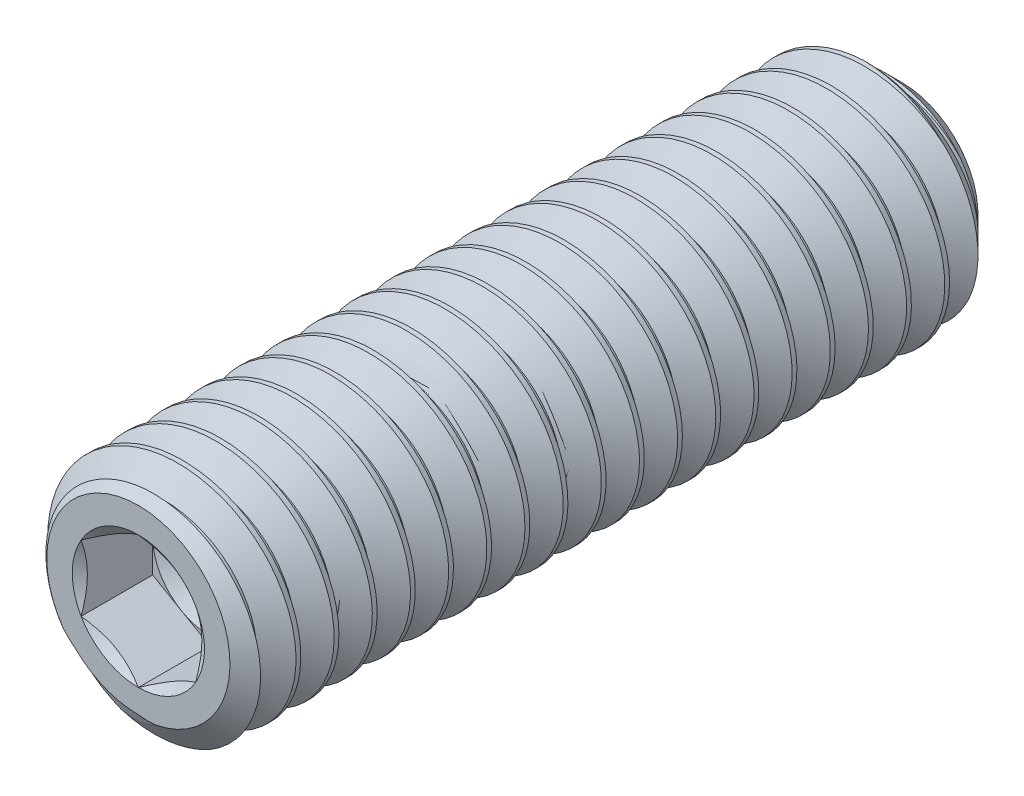
SolidWorks part; units mm, degrees
ref_plane "Front" through (0, 0, 0) normal (0, 0, 1) x (1, 0, 0)
ref_plane "Top" through (0, 0, 0) normal (0, 1, 0) x (1, 0, 0)
ref_plane "Right" through (0, 0, 0) normal (1, 0, 0) x (0, 0, -1)
sketch "Sketch22" plane through (0, 0, 0) normal (1, 0, 0) x (0, 0, -1)
  line L0 (-5, 0) -> (-5, 1.2)
  line L1 (-5, 1.2) -> (-4.7899, 1.5)
  line L2 (-4.7899, 1.5) -> (4.5, 1.5)
  line L3 (4.5, 1.5) -> (5, 1)
  line L4 (-0.145, 1.5) -> (-0.145, -1.5) construction
  line L5 (5, 0) -> (-5, 0)
  line L6 (-5, 1.2) -> (-5, -1.2) construction
  line L7 (5, 0) -> (5, 1)
  point P11 (-0.145, 0)
  dimension "D1" = 2.4
  dimension "Dia" = 3
  dimension "D2" = 0.5
  dimension "Length" = 10
  dimension "D3" = 35
  dimension "D6" = 45
revolve "Revolve1" add sketch "Sketch22" angle 360 about L5
ref_plane "Plane1" through (0, 0, -5) normal (0, 0, 1) x (1, 0, 0)
sketch "Sketch27" plane through (0, 0, -5) normal (0, 0, 1) x (1, 0, 0)
  circle A0 centre (0, 0) radius 1.5 construction
  circle A1 centre (0, 0) radius 1.5
curve "Helix/Spiral1" pitch 0.5 height 10.5 radius 1.5 centre (0, 0, -5) axis (0, 0, 1) start towards (0, 1, 0)
sketch "Sketch28" plane through (0, 0, 0) normal (1, 0, 0) x (0, 0, -1)
  line L0 (5, 1.5) -> (5.4375, 1.5)
  line L1 (5.4375, 1.5) -> (5.25, 1.1752)
  line L2 (5.25, 1.1752) -> (5.1875, 1.1752)
  line L3 (5.1875, 1.1752) -> (5, 1.5)
  line L4 (5.0937, 1.3376) -> (5.3437, 1.3376) construction
  line L6 (-4.7899, 1.5) -> (4.5, 1.5) construction
  dimension "D1" = 0.0625
  dimension "D2" = 0.25
  dimension "D3" = 60
sweep "Cut-Sweep2" cut profiles "Sketch28" path "Helix/Spiral1"
sketch "Sketch23" plane through (0, 0, 5) normal (0, 0, 1) x (1, 0, 0)
  line L1 (0, 0.866) -> (-0.75, 0.433)
  line L2 (-0.75, 0.433) -> (-0.75, -0.433)
  line L3 (-0.75, -0.433) -> (0, -0.866)
  line L4 (0, -0.866) -> (0.75, -0.433)
  line L5 (0.75, -0.433) -> (0.75, 0.433)
  line L6 (0.75, 0.433) -> (0, 0.866)
  circle A0 centre (0, 0) radius 0.75 construction
  dimension "Hex" = 1.5
extrude "Cut-Extrude10" cut sketch "Sketch23" against normal blind 0.9375
sketch "Sketch24" plane through (0, 0, 5) normal (0, 0, 1) x (1, 0, 0)
  circle A0 centre (0, 0) radius 0.866
extrude "Cut-Extrude11" cut sketch "Sketch24" against normal through all draft 55
sketch "Sketch26" plane through (0, 0, 4.0625) normal (0, 0, 1) x (1, 0, 0)
  circle A0 centre (0, 0) radius 0.75 construction
  circle A1 centre (0, 0) radius 0.75
extrude "Cut-Extrude12" cut sketch "Sketch26" against normal through all draft 60
sketch "Sketch30" plane through (0, 0, 0) normal (1, 0, 0) x (0, 0, -1)
  line L0 (-4.7899, 1.5) -> (4.5, 1.5) construction
  line L1 (-5, 0) -> (-5, 1.2) construction
  line L2 (5, 0) -> (5, 1) construction
  point P0 (-5, 1.5)
  point P1 (5, 1.5)
  point P2 (5, -1.5)
  point P11 (3.75, -1.5)
  dimension "D1" = 1.25
equation "\"D1@Sketch28\" = \"D4@Helix/Spiral1\" * .125"
equation "\"D2@Sketch28\" = \"D4@Helix/Spiral1\" * .5"
equation "\"D3@Helix/Spiral1\" = \"Length@Sketch22\" + \"D4@Helix/Spiral1\""
equation "\"D1@Sketch30\" = \"D4@Helix/Spiral1\" * 2.5"
equation "\"hex Depth@Cut-Extrude10\" = \"Hex@Sketch23\" * .625"
equation "\"D1@Sketch22\" = \"Dia@Sketch22\" * .8"
equation "\"D2@Sketch22\" = \"D4@Helix/Spiral1\""
